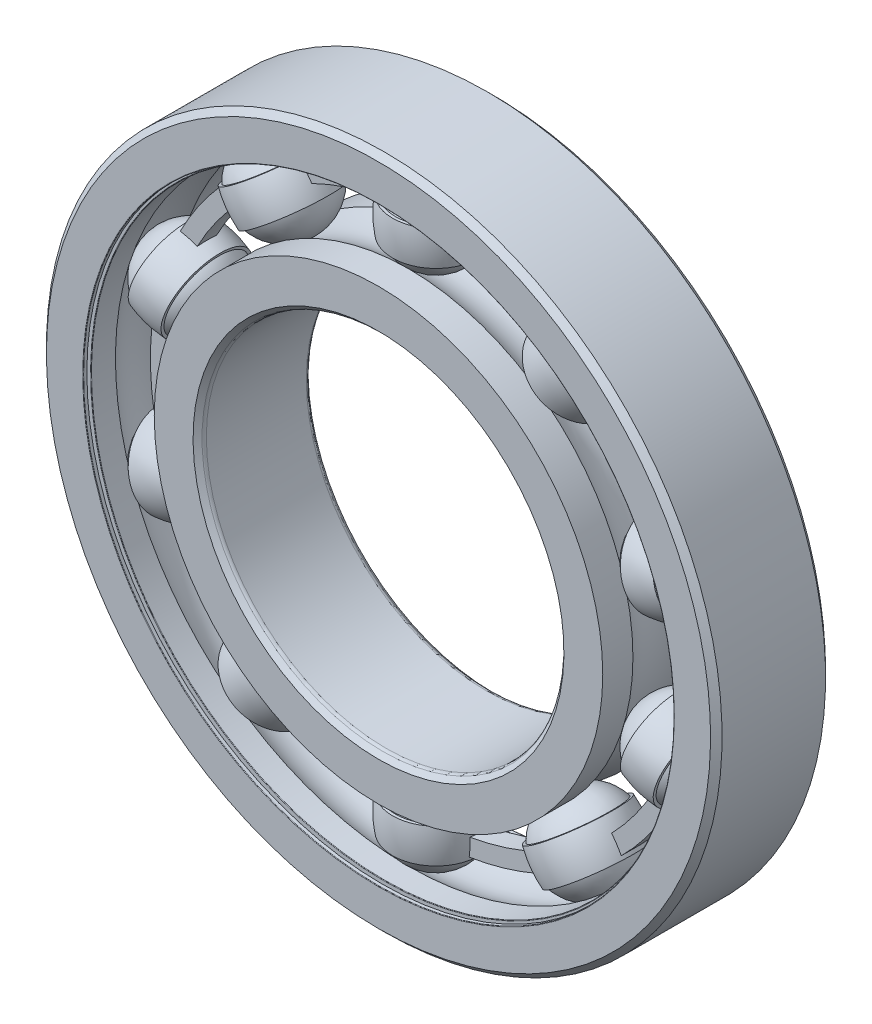
SolidWorks part; units mm, degrees
ref_plane "Front Plane" through (0, 0, 0) normal (0, 0, 1) x (1, 0, 0)
ref_plane "Top Plane" through (0, 0, 0) normal (0, 1, 0) x (1, 0, 0)
ref_plane "Right Plane" through (0, 0, 0) normal (1, 0, 0) x (0, 0, -1)
sketch "Sketch1" plane through (0, 0, 0) normal (0, 0, 1) x (1, 0, 0)
  line L0 (-23.5, 0) -> (23.5, 0) construction
  line L1 (-12.5, 0) -> (12.5, 0) construction
  circle A0 centre (0, 0) radius 12.5 construction
  circle A1 centre (0, 0) radius 23.5 construction
  point P3 (0, 0)
  point P6 (0, 0)
  point P7 (0, -12.5)
  point P11 (0, -23.5)
  point P12 (0, 12.5)
  point P13 (0, 23.5)
  dimension "OD" = 47
  dimension "ID" = 25
sketch "Sketch2" plane through (0, 0, 0) normal (1, 0, 0) x (0, 0, -1)
  line L0 (-4, 23.5) -> (4, 23.5) construction
  line L1 (0, 23.5) -> (0, -23.5) construction
  line L2 (3.6, 23.5) -> (-3.6, 23.5)
  line L3 (-3.6, 23.5) -> (-4, 23.1)
  line L4 (-4, 23.1) -> (-4, 20.4)
  line L5 (-4, 20.4) -> (-1.9, 20.4)
  line L6 (4, 20.4) -> (1.9, 20.4)
  line L7 (4, 23.1) -> (4, 20.4)
  line L8 (3.6, 23.5) -> (4, 23.1)
  line L9 (0, 23.5) -> (0, 18) construction
  line L10 (0, 18) -> (0, 12.5) construction
  line L11 (0, 23.5) -> (0, -23.5) construction
  line L12 (-4, 0) -> (4, 0) construction
  line L13 (4, 12.5) -> (-4, 12.5) construction
  line L14 (0, 21.061) -> (0, 14.939) construction
  line L15 (-4, -12.5) -> (4, -12.5) construction
  line L16 (-4, -12.5) -> (-4, 12.5) construction
  line L17 (4, 23.5) -> (4, -23.5) construction
  arc A0 (-1.9, 20.4) -> (1.9, 20.4) centre (0, 18) cw
  circle A1 centre (0, 18) radius 3.061 construction
  point P14 (0, 12.5)
  point P17 (0, 0)
  point P21 (0, 23.5)
  point P29 (0, 12.5)
  point P30 (0, -12.5)
  point P35 (0, 21.061)
  dimension "Approx. Ball Dia." = 6.1221
  dimension "Width" = 8
  dimension "D1" = 45
  dimension "D2" = 0.4
  dimension "D3" = 3.8
  dimension "D4" = 2.4
  dimension "For Shaft Diameter" = 25
  dimension "For Housing ID" = 47
sketch "Sketch3" plane through (0, 0, 0) normal (1, 0, 0) x (0, 0, -1)
  line L0 (3.6, 23.5) -> (4, 23.1) construction
  line L1 (4, 23.1) -> (4, 20.4) construction
  line L2 (4, 20.4) -> (1.9, 20.4) construction
  line L3 (-4, 20.4) -> (-1.9, 20.4) construction
  line L4 (-4, 23.1) -> (-4, 20.4) construction
  line L5 (-3.6, 23.5) -> (-4, 23.1) construction
  line L6 (3.6, 23.5) -> (-3.6, 23.5) construction
  line L7 (3.6, 23.5) -> (4, 23.1)
  line L8 (4, 23.1) -> (4, 20.4)
  line L9 (4, 20.4) -> (1.9, 20.4)
  line L10 (-4, 20.4) -> (-1.9, 20.4)
  line L11 (-4, 23.1) -> (-4, 20.4)
  line L12 (-3.6, 23.5) -> (-4, 23.1)
  line L13 (3.6, 23.5) -> (-3.6, 23.5)
  arc A0 (1.9, 20.4) -> (-1.9, 20.4) centre (0, 18) ccw construction
  arc A1 (1.9, 20.4) -> (-1.9, 20.4) centre (0, 18) ccw
revolve "Revolve1" add sketch "Sketch3" angle 360 about L12
sketch "Sketch8" plane through (0, 0, 0) normal (1, 0, 0) x (0, 0, -1)
  line L0 (-4, 20.4) -> (-1.9, 20.4) construction
  line L1 (-3.744, 20.4) -> (-3.6, 20.4)
  line L2 (-3.744, 20.4) -> (-3.744, 21.4333) construction
  line L3 (-3.744, 21.4333) -> (-3.6, 21.4333)
  line L4 (-3.6, 20.4) -> (-3.6, 21.4333)
  line L5 (4, 20.4) -> (1.9, 20.4) construction
  line L6 (3.6, 20.4) -> (3.744, 20.4)
  line L7 (3.6, 20.4) -> (3.6, 21.4333)
  line L8 (3.6, 21.4333) -> (3.744, 21.4333)
  line L9 (3.744, 20.4) -> (3.744, 21.4333) construction
  line L10 (-3.6, 21.4333) -> (3.6, 21.4333) construction
  line L11 (0, 23.5) -> (0, -23.5) construction
  line L12 (-3.744, 21.4333) -> (-3.744, 22.4667) construction
  line L13 (-3.744, 22.4667) -> (-3.744, 23.5) construction
  line L14 (-4, 23.5) -> (4, 23.5) construction
  line L15 (-3.744, 20.4) -> (-4, 20.4)
  line L16 (-4, 20.4) -> (-4, 20.544)
  line L17 (-4, 23.1) -> (-4, 20.4) construction
  line L18 (-4, 20.544) -> (-3.744, 20.544)
  line L19 (-3.744, 20.544) -> (-3.744, 21.4333)
  line L20 (3.744, 20.4) -> (4, 20.4)
  line L21 (4, 20.4) -> (4, 20.544)
  line L22 (4, 23.1) -> (4, 20.4) construction
  line L23 (4, 20.544) -> (3.744, 20.544)
  line L24 (3.744, 20.544) -> (3.744, 21.4333)
  point P12 (0, 21.4333)
  dimension "D1" = 7.2
  dimension "D2" = 0.144
revolve "Cut-Revolve1" cut sketch "Sketch8" angle 360 about L12
sketch "Sketch4" plane through (0, 0, 0) normal (1, 0, 0) x (0, 0, -1)
  line L0 (0, 23.5) -> (0, -23.5) construction
  line L1 (0, 23.5) -> (0, -23.5) construction
  line L2 (-3.6, 12.5) -> (-4, 12.9)
  line L3 (-4, 12.9) -> (-4, 15.6)
  line L5 (-4, 15.6) -> (-1.9, 15.6)
  line L6 (-3.6, 12.5) -> (3.6, 12.5)
  line L8 (3.6, 12.5) -> (4, 12.9)
  line L10 (4, 12.9) -> (4, 15.6)
  line L11 (4, 15.6) -> (1.9, 15.6)
  line L12 (-4, 23.1) -> (-4, 20.4) construction
  line L13 (3.6, 23.5) -> (4, 23.1) construction
  line L15 (4, -23.1) -> (4, 23.1) construction
  line L16 (3.6, 23.5) -> (3.6, -23.5) construction
  arc A1 (1.9, 15.6) -> (-1.9, 15.6) centre (0, 18) cw
  circle A2 centre (0, 18) radius 3.061 construction
  point P1 (0, 12.5)
revolve "Revolve2" add sketch "Sketch4" angle 360 about L12
sketch "Sketch5" plane through (0, 0, 0) normal (1, 0, 0) x (0, 0, -1)
  line L0 (-3.061, 18) -> (3.061, 18)
  arc A2 (-3.061, 18) -> (3.061, 18) centre (0, 18) cw
  arc A3 (1.9, 20.4) -> (-1.9, 20.4) centre (0, 18) ccw construction
revolve "Revolve3" add sketch "Sketch5" angle 360 about L0
sketch "Sketch6" plane through (0, 0, 0) normal (1, 0, 0) x (0, 0, -1)
  line L0 (-1.9, 20.4) -> (-1.9, 19.2) construction
  line L1 (-1.9, 19.2) -> (-1.9, 18) construction
  line L2 (-1.9, 18) -> (-1.9, 16.8) construction
  line L3 (-1.9, 16.8) -> (-1.9, 15.6) construction
  line L4 (-4, 19.2) -> (-3.8027, 19.2) construction
  line L5 (-1.9, 19.2) -> (-1.9, 16.8) construction
  line L7 (-3.8027, 19.2) -> (-3.6053, 19.2) construction
  line L8 (-3.6053, 19.2) -> (-3.408, 19.2) construction
  line L10 (0, 23.5) -> (0, -23.5) construction
  line L11 (0, 23.5) -> (0, -23.5) construction
  line L12 (-4, 20.4) -> (-4, 19.2) construction
  line L13 (-3.0134, 19.2) -> (-2.816, 19.2) construction
  line L14 (-4, 23.1) -> (-4, -23.1) construction
  line L15 (-4, 19.2) -> (-4, 18) construction
  line L16 (-4, 18) -> (-4, 16.8) construction
  line L17 (-4, 16.8) -> (-4, 15.6) construction
  line L18 (-3.408, 19.2) -> (-3.2107, 19.2) construction
  line L19 (-3.2107, 19.2) -> (-3.0134, 19.2) construction
  line L20 (-2.816, 19.2) -> (-3.0134, 19.2)
  line L21 (-4, 16.8) -> (-3.8027, 16.8) construction
  line L22 (-3.8027, 16.8) -> (-3.6053, 16.8) construction
  line L23 (-3.6053, 16.8) -> (-3.408, 16.8) construction
  line L24 (-3.408, 16.8) -> (-3.2107, 16.8) construction
  line L25 (-3.2107, 16.8) -> (-3.0134, 16.8) construction
  line L26 (-3.0134, 16.8) -> (-2.816, 16.8) construction
  line L27 (-2.816, 16.8) -> (-3.0134, 16.8)
  line L28 (-3.2107, 19.2) -> (-3.2107, 16.8) construction
  line L30 (-3.112, 19.2) -> (-3.112, 16.8) construction
  circle A0 centre (0, 18) radius 3.061 construction
  arc A2 (-3.0134, 16.8) -> (-3.0134, 19.2) centre (4.2348, 18) cw
  arc A3 (-2.816, 19.2) -> (-2.816, 16.8) centre (0, 18) ccw
revolve "Revolve4" add sketch "Sketch6" angle 360 about L11
sketch "Sketch7" plane through (0, 0, 0) normal (0, 0, 1) x (1, 0, 0)
  line L0 (-3.061, 18) -> (3.061, 18) construction
  line L1 (0, 14.939) -> (0, 21.061) construction
  line L2 (0, 0) -> (5.7585, 17.054) construction
  line L8 (0, 23.5) -> (0, -23.5) construction
  line L9 (10.9118, 14.3155) -> (11.6392, 15.2699)
  line L10 (0, 23.5) -> (0, -23.5) construction
  line L11 (0, 19.2) -> (0, 18)
  arc A1 (10.9118, 14.3155) -> (0, 18) centre (0, 0) ccw
  arc A2 (11.6392, 15.2699) -> (0, 19.2) centre (0, 0) ccw
  dimension "D1" = 37.316
  dimension "D2" = 6.1221
extrude "Boss-Extrude1" add sketch "Sketch7" along normal mid plane 1.3333
pattern_circular "CirPattern1" count 10 over 360 about axis through (0, 0, 4) along (0, 0, -1) of bodies 104 134
pattern_circular "CirPattern2" count 10 over 360 about axis through (0, 0, 4) along (0, 0, -1) of "Revolve4", "Boss-Extrude1" reverse direction yes
fillet "Fillet1" radius 0.036 4 edges at (0, -20.4, -3.6) (0, -20.544, -4) (0, -20.4, 3.6) (0, -20.544, 4)
fillet "Fillet2" radius 0.3 2 edges at (0, -12.5, -3.6) (0, -12.5, 3.6)
ref_plane "Plane1" through (5.7585, 17.054, 0) normal (0.3199, 0.9474, 0) x (0.9474, -0.3199, 0)
sketch "Sketch9" plane through (5.7585, 17.054, 0) normal (0.3199, 0.9474, 0) x (0.9474, -0.3199, 0)
  line L0 (-2.8584, -0.6667) -> (-2.8584, -2)
  line L1 (-2.8584, -2) -> (-1.2398, -2)
  line L2 (-1.2398, -2) -> (0, -0.9596)
  line L3 (0, -0.9596) -> (1.2398, -2)
  line L4 (1.2398, -2) -> (2.8584, -2)
  line L5 (2.8584, -2) -> (2.8584, -0.6667)
  line L6 (2.8584, -0.6667) -> (-2.8584, -0.6667)
  line L7 (0, -0.6667) -> (0, 0) construction
  line L8 (-2.8584, -0.6667) -> (-2.8584, 0) construction
  dimension "D1" = 1.3333
  dimension "D2" = 0.6667
  dimension "D3" = 40
extrude "Boss-Extrude2" [suppressed] add sketch "Sketch9" along normal blind 2.6784 draft 15 and the other way blind 2.6784 draft 10 separate body draft outward yes other way draft outward yes
fillet "Fillet3" [suppressed] radius 0.4
mirror "Mirror1" [suppressed] about plane through (0, 0, 0) normal (0, 0, 1) of bodies 149
pattern_circular "CirPattern3" [suppressed] count 10 over 360 about axis through (0, 0, 4) along (0, 0, -1) of bodies 158 149
equation "\"D2@Sketch2\" = \"Width@Sketch2\" * .05"
equation "\"D3@Sketch2\"=\"Width@Sketch2\" * .475"
equation "\"D4@Sketch2\" =  (  (  ( \"OD@Sketch1\" - \"Width@Sketch2\" )  / 2 )  / 3.25 )  / 2.5"
equation "\"D1@Boss-Extrude1\" = \"Width@Sketch2\" / 6"
equation "\"D1@Sketch8\"=\"Width@Sketch2\"*.9"
equation "\"D2@Sketch8\"=\"D1@Sketch8\"*.02"
equation "\"D1@Fillet1\" = \"D2@Sketch8\" * .25"
equation "\"D1@Fillet2\" = \"D2@Sketch2\" * .75"
equation "\"Approx No of Balls\"= ( pi * \"OD@Sketch1\" ) * .4 / \"Approx. Ball Dia.@Sketch2\""
equation "\"D1@CirPattern1\"=\"Approx No of Balls\""
equation "\"D1@Sketch7\"=360/\"Approx No of Balls\""
equation "\"D1@CirPattern2\"=\"Approx No of Balls\""
equation "\"D2@Sketch7\"=\"Approx. Ball Dia.@Sketch2\""
equation "\"D2@Sketch9\"=\"d1@boss-extrude1\"*.5"
equation "\"D1@Sketch9\"=\"D2@Sketch9\"*2"
equation "\"D1@Boss-Extrude2\"=\"Approx. Ball Dia.@Sketch2\"*.4375"
equation "\"D2@Boss-Extrude2\"=\"D1@Boss-Extrude2\""
equation "\"D1@CirPattern3\"=\"Approx No of Balls\""
equation "\"D1@Fillet3\"=\"D1@Sketch9\" * .3"
